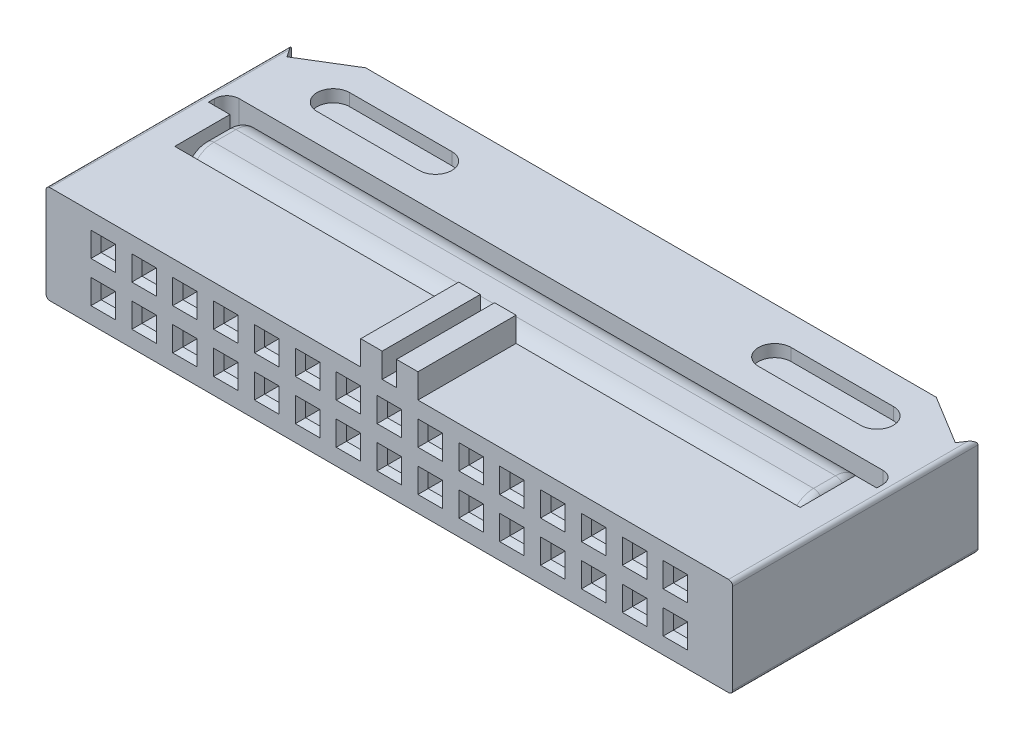
SolidWorks part; units mm, degrees
extrude "Base-Extrude" add sketch "Sketch1" against normal blind 16.256
sketch "Sketch1" plane through (0, 0, 0) normal (0, 0, 1) x (1, 0, 0)
  line L1 (-21.082, 3.048) -> (-1.778, 3.048)
  line L2 (-21.336, 2.794) -> (-21.336, -2.794)
  line L3 (-21.082, -3.048) -> (21.082, -3.048)
  line L4 (21.336, 2.794) -> (21.336, -2.794)
  line L5 (0, -6.7653) -> (0, 6.7653) construction
  line L6 (16.5234, 0) -> (-16.5234, 0) construction
  line L7 (1.778, 3.048) -> (21.082, 3.048)
  line L8 (-1.778, 4.572) -> (-0.4445, 4.572)
  line L9 (-1.778, 4.572) -> (-1.778, 3.048)
  line L10 (0.4445, 4.572) -> (1.778, 4.572)
  line L11 (1.778, 4.572) -> (1.778, 3.048)
  line L13 (-0.4445, 4.572) -> (-0.4445, 3.048)
  line L14 (-0.4445, 3.048) -> (0.4445, 3.048)
  line L15 (0.4445, 4.572) -> (0.4445, 3.048)
  arc A0 (-21.082, 3.048) -> (-21.336, 2.794) centre (-21.082, 2.794) ccw
  arc A1 (-21.336, -2.794) -> (-21.082, -3.048) centre (-21.082, -2.794) ccw
  arc A2 (21.336, -2.794) -> (21.082, -3.048) centre (21.082, -2.794) cw
  arc A3 (21.082, 3.048) -> (21.336, 2.794) centre (21.082, 2.794) cw
  point P4 (0, 3.048)
  point P7 (-21.336, 0)
  point P14 (0, 4.572)
  point P15 (0, 3.048)
  point P26 (21.336, -3.048)
  point P29 (21.336, 3.048)
  dimension "D8" = 0.254
  dimension "D9" = 0.254
  dimension "D1" = 42.672
  dimension "D2" = 6.096
  dimension "D3" = 3.556
  dimension "D4" = 1.524
  dimension "D5" = 0.889
  dimension "D6" = 1.778
  dimension "D7" = 21.336
ref_plane "Front" through (0, 0, 0) normal (0, 0, 1) x (1, 0, 0)
ref_plane "Top" through (0, 0, 0) normal (0, 1, 0) x (1, 0, 0)
ref_plane "Right" through (0, 0, 0) normal (1, 0, 0) x (0, 0, -1)
sketch "Sketch2" plane through (0, 3.048, 0) normal (0, 1, 0) x (-1, 0, 0)
  line L0 (-17.7294, -16.256) -> (-20.7645, -14.403)
  line L1 (-20.7645, -14.403) -> (-21.336, -15.2431)
  line L2 (21.336, -16.256) -> (21.336, -15.2431)
  line L3 (0, -17.4041) -> (0, 0.7826) construction
  line L4 (20.7645, -14.403) -> (21.336, -15.2431)
  line L5 (17.7294, -16.256) -> (20.7645, -14.403)
  line L6 (21.336, -16.256) -> (17.7294, -16.256)
  line L7 (-21.336, -16.256) -> (-21.336, -15.2431)
  line L8 (-21.336, -16.256) -> (-17.7294, -16.256)
  line L11 (-20.0025, -10.668) -> (20.0025, -10.668)
  line L12 (-20.7645, -9.525) -> (20.7645, -9.525)
  line L13 (-20.7645, -9.906) -> (-20.7645, -9.525)
  line L14 (20.7645, -9.906) -> (20.7645, -9.525)
  line L15 (0, 6.7653) -> (0, -6.7653) construction
  line L16 (-21.336, -16.256) -> (-21.336, 0) construction
  line L17 (-21.082, -16.256) -> (-1.778, -16.256) construction
  arc A0 (-20.7645, -9.906) -> (-20.0025, -10.668) centre (-20.0025, -9.906) ccw
  arc A1 (20.7645, -9.906) -> (20.0025, -10.668) centre (20.0025, -9.906) cw
  point P20 (0, -10.668)
  point P24 (0, -9.525)
  dimension "D1" = 0.762
  dimension "D2" = 40.005
  dimension "D3" = 5.588
  dimension "D4" = 1.143
  dimension "D5" = 3.556
  dimension "D6" = 1.016
  dimension "D7" = 1.853
extrude "Cut-Extrude1" cut sketch "Sketch2" against normal through all
sketch "Sketch3" plane through (-1.778, 0, 0) normal (-1, 0, 0) x (0, 0, 1)
  line L0 (0, -6.3682) -> (0, 6.3682) construction
  line L1 (-16.256, 4.572) -> (-6.096, 4.572)
  line L2 (-16.256, 4.572) -> (-16.256, 3.048)
  line L3 (-16.256, 3.048) -> (-6.096, 3.048)
  line L4 (-6.096, 4.572) -> (-6.096, 3.048)
  line L5 (-14.8697, 3.048) -> (0, 3.048) construction
  dimension "D1" = 6.096
extrude "Cut-Extrude2" cut sketch "Sketch3" against normal through all
sketch "Sketch4" plane through (0, 0, 0) normal (0, 0, 1) x (1, 0, 0)
  line L0 (-12.4713, 1.27) -> (21.336, 1.27) construction
  line L1 (-12.4713, -1.27) -> (21.336, -1.27) construction
  line L2 (17.78, 3.048) -> (17.78, -3.048) construction
  line L4 (21.336, -2.794) -> (21.336, 2.794) construction
  line L6 (21.336, 1.27) -> (21.336, -1.27) construction
  line L7 (16.5234, 0) -> (-16.5234, 0) construction
  line L8 (17.3355, -0.8255) -> (18.2245, -0.8255)
  line L9 (17.3355, -0.8255) -> (17.3355, -1.7145)
  line L10 (17.3355, -1.7145) -> (18.2245, -1.7145)
  line L11 (17.3355, 1.7145) -> (18.2245, 1.7145)
  line L12 (17.3355, 1.7145) -> (17.3355, 0.8255)
  line L13 (17.3355, 0.8255) -> (18.2245, 0.8255)
  line L14 (18.2245, 1.7145) -> (18.2245, 0.8255)
  line L15 (18.2245, -0.8255) -> (18.2245, -1.7145)
  point P11 (21.336, 0)
  point P16 (18.2245, -1.27)
  point P17 (17.3355, -1.27)
  point P23 (17.78, 1.7145)
  point P24 (18.2245, 1.27)
  point P25 (17.78, -1.7145)
  dimension "D1" = 3.556
  dimension "D2" = 0.889
  dimension "D3" = 2.54
  dimension "D4" = 0.889
  dimension "D6" = 0.889
  dimension "D7" = 0.889
extrude "Cut-Extrude3" cut sketch "Sketch4" against normal up to surface (6.096 mm away) up to face at (1.1113, 3.81, -6.096)
sketch "Sketch5" plane through (0, 0, 0) normal (0, 0, 1) x (1, 0, 0)
  line L1 (17.018, 2.032) -> (18.542, 2.032)
  line L2 (17.018, 2.032) -> (17.018, 0.508)
  line L3 (17.018, 0.508) -> (18.542, 0.508)
  line L4 (18.542, 2.032) -> (18.542, 0.508)
  line L5 (17.018, -0.508) -> (18.542, -0.508)
  line L6 (17.018, -0.508) -> (17.018, -2.032)
  line L7 (17.018, -2.032) -> (18.542, -2.032)
  line L8 (18.542, -0.508) -> (18.542, -2.032)
  line L11 (17.78, 2.032) -> (17.78, 0.508) construction
  line L12 (17.018, 1.27) -> (18.542, 1.27) construction
  line L14 (18.2245, 0.8255) -> (18.2245, 1.7145) construction
  line L15 (17.3355, 0.8255) -> (18.2245, 0.8255) construction
  line L16 (17.3355, -1.7145) -> (18.2245, -1.7145) construction
  line L17 (18.2245, -0.8255) -> (17.3355, -0.8255) construction
  point P10 (17.78, 2.032)
  point P17 (17.78, -1.7145)
  dimension "D1" = 0.3175
  dimension "D2" = 1.524
  dimension "D3" = 1.524
  dimension "D4" = 0.3175
  dimension "D5" = 0.3175
  dimension "D6" = 0.3175
extrude "Cut-Extrude4" cut sketch "Sketch5" against normal blind 0.762 draft 45
pattern_linear "LPattern1" count 15 spacing 2.54 along (-1, 0, 0) of "Cut-Extrude3", "Cut-Extrude4"
sketch "Sketch6" plane through (0, 0, 0) normal (1, 0, 0) x (0, 0, -1)
  line L0 (6.096, 3.048) -> (6.096, -3.048)
  line L1 (10.668, 3.048) -> (6.096, 3.048)
  line L2 (10.668, 3.048) -> (10.668, 1.778)
  line L3 (10.668, 1.778) -> (7.874, 1.778)
  line L4 (7.366, 1.27) -> (7.366, -3.048)
  line L5 (6.096, -3.048) -> (7.366, -3.048)
  line L6 (6.096, 4.572) -> (6.096, 3.048) construction
  arc A0 (7.874, 1.778) -> (7.366, 1.27) centre (7.874, 1.27) ccw
  dimension "D1" = 0.508
  dimension "D2" = 1.27
  dimension "D3" = 1.27
extrude "Cut-Extrude5" cut sketch "Sketch6" against normal mid plane 38.862
sketch "Sketch7" plane through (0, 0, -16.256) normal (0, 0, -1) x (-1, 0, 0)
  line L0 (-20.7645, -3.048) -> (-20.7645, 3.048) construction
  line L1 (-20.5105, -2.413) -> (20.5105, -2.413)
  line L2 (-20.7645, -2.667) -> (-20.7645, -3.048)
  line L3 (-20.7645, -3.048) -> (20.7645, -3.048)
  line L4 (20.7645, -2.667) -> (20.7645, -3.048)
  arc A0 (-20.5105, -2.413) -> (-20.7645, -2.667) centre (-20.5105, -2.667) ccw
  arc A1 (20.5105, -2.413) -> (20.7645, -2.667) centre (20.5105, -2.667) cw
  dimension "D1" = 0.254
  dimension "D2" = 0.635
extrude "Cut-Extrude6" cut sketch "Sketch7" against normal up to surface (6.731 mm away) up to face at (0, 1.2065, -9.525)
sketch "Sketch8" plane through (0, 3.048, 0) normal (0, 1, 0) x (-1, 0, 0)
  line L0 (-16.891, -14.4272) -> (-10.541, -14.4272)
  line L1 (-10.541, -12.3952) -> (-16.891, -12.3952)
  line L2 (-21.336, -15.2431) -> (-21.336, 0) construction
  line L3 (-17.7294, -16.256) -> (17.7294, -16.256) construction
  line L4 (0, -20.4815) -> (0, -9.8087) construction
  line L5 (10.541, -12.3952) -> (16.891, -12.3952)
  line L6 (16.891, -14.4272) -> (10.541, -14.4272)
  arc A0 (-10.541, -14.4272) -> (-10.541, -12.3952) centre (-10.541, -13.4112) ccw
  arc A1 (-16.891, -12.3952) -> (-16.891, -14.4272) centre (-16.891, -13.4112) ccw
  arc A2 (10.541, -14.4272) -> (10.541, -12.3952) centre (10.541, -13.4112) cw
  arc A3 (16.891, -12.3952) -> (16.891, -14.4272) centre (16.891, -13.4112) cw
  dimension "D1" = 1.016
  dimension "D2" = 6.35
  dimension "D3" = 4.445
  dimension "D4" = 2.8448
extrude "Cut-Extrude7" cut sketch "Sketch8" against normal blind 0.762
fillet "Fillet1" radius 0.254 1 edges at (0, 1.778, -9.525)
ref_plane "Plane1" through (0, 0, 0) normal (0, 1, 0) x (-1, 0, 0)
sketch "Sketch12" plane through (0, 0, -16.256) normal (0, 0, -1) x (-1, 0, 0)
  line L0 (-17.7294, 0) -> (17.7294, 0) construction
  line L1 (-17.7294, -2.413) -> (-17.7294, 3.048) construction
  line L2 (17.7294, -2.413) -> (17.7294, 3.048) construction
  point P7 (0, 0)
sketch "Sketch9" plane through (0, -3.048, 0) normal (0, -1, 0) x (1, 0, 0)
  line L0 (0, -9.525) -> (0, -10.668) construction
  line L1 (-20.7645, -9.525) -> (20.7645, -9.525) construction
  line L2 (-20.0025, -10.668) -> (20.0025, -10.668) construction
  point P6 (0, -10.0965)
other "CPoint1"
ref_axis "Axis1" through (0, 0, -26.256) along (0, 0, 1)
sketch "Sketch10" plane through (0, -3.048, 0) normal (0, -1, 0) x (1, 0, 0)
  line L0 (-18.6292, -6.731) -> (18.6292, -6.731) construction
  line L1 (-18.6292, -6.1718) -> (18.6292, -6.1718)
  line L2 (-18.6292, -7.2902) -> (18.6292, -7.2902)
  arc A0 (-18.6292, -6.1718) -> (-18.6292, -7.2902) centre (-18.6292, -6.731) ccw
  arc A1 (18.6292, -7.2902) -> (18.6292, -6.1718) centre (18.6292, -6.731) ccw
  point P2 (0, -6.731)
sketch "Sketch11" plane through (0, 0, 0) normal (1, 0, 0) x (0, 0, -1)
  line L0 (6.731, -3.048) -> (6.731, 1.2952)
  line L1 (7.731, 2.2952) -> (9.0965, 2.2952)
  line L2 (10.0965, 1.2952) -> (10.0965, -3.048)
  arc A0 (6.731, 1.2952) -> (7.731, 2.2952) centre (7.731, 1.2952) cw
  arc A1 (9.0965, 2.2952) -> (10.0965, 1.2952) centre (9.0965, 1.2952) cw
  dimension "D1" = 1
sweep "Sweep1" add profiles "Sketch10" path "Sketch11"
